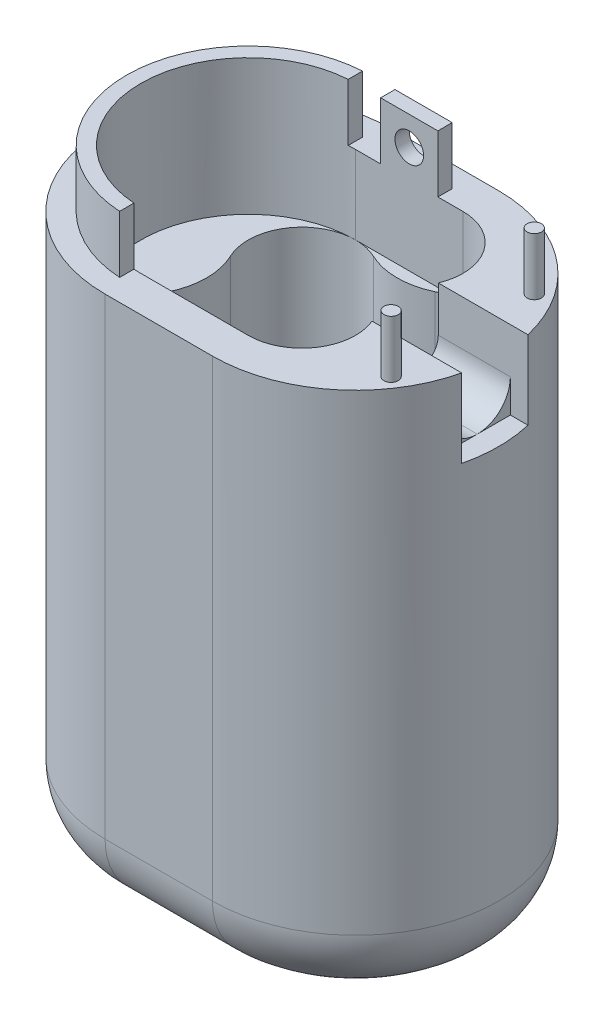
SolidWorks part; units mm, degrees
ref_plane "Front Plane" through (0, 0, 0) normal (0, 0, 1) x (1, 0, 0)
ref_plane "Top Plane" through (0, 0, 0) normal (0, 1, 0) x (1, 0, 0)
ref_plane "Right Plane" through (0, 0, 0) normal (1, 0, 0) x (0, 0, -1)
sketch "Sketch1" plane through (0, 0, 0) normal (0, 1, 0) x (1, 0, 0)
  line L0 (0, 0) -> (-23.105, 0) construction
  line L1 (-7.5, 0) -> (7.5, 0) construction
  line L2 (0, 13.7042) -> (0, -14.0987) construction
  line L3 (-7.5, 20) -> (7.5, 20)
  line L4 (-7.5, -20) -> (7.5, -20)
  arc A0 (-4.2857, 14.2763) -> (-14.2763, 4.2857) centre (-7.5, 7.5) ccw
  arc A1 (4.2857, 14.2763) -> (14.2763, 4.2857) centre (7.5, 7.5) cw
  arc A2 (4.2857, -14.2763) -> (14.2763, -4.2857) centre (7.5, -7.5) ccw
  arc A3 (-4.2857, -14.2763) -> (-14.2763, -4.2857) centre (-7.5, -7.5) cw
  arc A4 (14.2763, -4.2857) -> (14.2763, 4.2857) centre (23.3114, 0) cw
  arc A5 (-4.2857, -14.2763) -> (4.2857, -14.2763) centre (0, -23.3114) cw
  arc A6 (-14.2763, 4.2857) -> (-14.2763, -4.2857) centre (-23.3114, 0) cw
  arc A7 (-4.2857, 14.2763) -> (4.2857, 14.2763) centre (0, 23.3114) ccw
  arc A8 (-7.5, 20) -> (-7.5, -20) centre (-7.5, 0) ccw
  arc A9 (7.5, -20) -> (7.5, 20) centre (7.5, 0) ccw
  point P5 (0, 0)
  point P16 (7.5, 0)
  point P19 (0, -7.5)
  point P22 (-7.5, 0)
  point P25 (0, 7.5)
  dimension "D1" = 15
  dimension "D2" = 10
  dimension "D3" = 40
extrude "Boss-Extrude1" add sketch "Sketch1" along normal blind 55
sketch "Sketch2" plane through (0, 0, 0) normal (0, -1, 0) x (1, 0, 0)
  line L0 (-7.5, 0) -> (7.5, 0) construction
  line L1 (-7.5, 20) -> (7.5, 20)
  line L2 (-7.5, -20) -> (7.5, -20)
  line L3 (7.5, -20) -> (-7.5, -20) construction
  arc A0 (-7.5, 20) -> (-7.5, -20) centre (-7.5, 0) ccw
  arc A1 (7.5, -20) -> (7.5, 20) centre (7.5, 0) ccw
  arc A2 (-7.5, 20) -> (-7.5, -20) centre (-7.5, 0) ccw construction
  point P3 (0, 0)
extrude "Boss-Extrude2" add sketch "Sketch2" along normal blind 10
fillet "Fillet1" radius 10 4 edges at (27.5, -10, 0) (0, -10, -20) (-27.5, -10, 0) (0, -10, 20)
sketch "Sketch4" plane through (0, 55, 0) normal (0, 1, 0) x (1, 0, 0)
  line L0 (-7.5, -20) -> (7.5, -20) construction
  line L1 (-7.5, 20) -> (7.5, 20)
  line L2 (-7.5, -20) -> (7.5, -20)
  line L3 (27.5, 0) -> (27.5, 4.625) construction
  line L4 (14.4271, 4.625) -> (26.9579, 4.625)
  line L5 (7.5, 20) -> (-7.5, 20) construction
  line L6 (14.4271, -4.625) -> (26.9579, -4.625)
  line L7 (-7.5, 15) -> (7.5, 15)
  line L9 (27.5, 0) -> (27.5, -4.625) construction
  line L10 (7.5, -15) -> (-7.5, -15)
  arc A0 (-7.5, 20) -> (-7.5, -20) centre (-7.5, 0) ccw
  arc A1 (7.5, -20) -> (26.9579, -4.625) centre (7.5, 0) ccw
  arc A2 (-7.5, 20) -> (-7.5, -20) centre (-7.5, 0) ccw construction
  arc A3 (7.5, -15) -> (14.4271, -4.625) centre (7.5, -7.5) ccw
  arc A4 (-7.5, 15) -> (-7.5, -15) centre (-7.5, 0) ccw
  arc A5 (4.2857, -14.2763) -> (14.2763, -4.2857) centre (7.5, -7.5) ccw construction
  arc A6 (-14.2763, -4.2857) -> (-4.2857, -14.2763) centre (-7.5, -7.5) ccw construction
  arc A7 (14.4271, 4.625) -> (7.5, 15) centre (7.5, 7.5) ccw
  arc A12 (26.9579, 4.625) -> (7.5, 20) centre (7.5, 0) ccw
  arc A14 (7.5, -20) -> (7.5, 20) centre (7.5, 0) ccw construction
  point P3 (0, 0)
  dimension "D1" = 9.25
  dimension "D2" = 5
extrude "Boss-Extrude3" add sketch "Sketch4" along normal blind 10.95
fillet "Fillet3" radius 4.625 2 edges at (20.6925, 55, 4.625) (20.6925, 55, -4.625)
ref_plane "Plane1" through (27.5, 0, 0) normal (1, 0, 0) x (0, 0, -1)
sketch "Sketch5" plane through (27.5, 0, 0) normal (1, 0, 0) x (0, 0, -1)
  line L0 (4.625, 65.95) -> (4.625, 59.625) construction
  line L1 (-4.625, 65.95) -> (4.625, 65.95)
  line L2 (-4.625, 65.95) -> (-4.625, 55)
  line L3 (-4.625, 55) -> (4.625, 55)
  line L4 (4.625, 65.95) -> (4.625, 55)
extrude "Cut-Extrude1" cut sketch "Sketch5" against normal blind 3
sketch "Sketch6" plane through (0, 65.95, 0) normal (0, 1, 0) x (1, 0, 0)
  line L0 (-7.5, 15) -> (7.5, 15) construction
  line L1 (-4, 17) -> (4, 17)
  line L2 (-4, 17) -> (-4, 15)
  line L3 (-4, 15) -> (4, 15)
  line L4 (4, 17) -> (4, 15)
  line L5 (0, 15) -> (0, 0) construction
  line L8 (22.4666, 10) -> (22.4666, -10) construction
  line L9 (0, 0) -> (22.4666, 0) construction
  line L10 (22.4666, 10) -> (24.1296, 11.1111) construction
  line L11 (23.574, 11.9426) -> (24.6851, 10.2796) construction
  line L12 (22.4666, -10) -> (24.1296, -11.1111) construction
  line L13 (24.5, 0) -> (13.3114, 0) construction
  line L14 (23.574, -11.9426) -> (24.6851, -10.2796) construction
  line L15 (-8.5, 16.9706) -> (-8.5, 14.9666)
  line L16 (-8.5, -14.9666) -> (-8.5, -16.9706)
  circle A0 centre (22.4666, -10) radius 1
  circle A1 centre (22.4666, 10) radius 1
  arc A2 (-8.5, 14.9666) -> (-8.5, -14.9666) centre (-7.5, 0) ccw
  arc A3 (-8.5, 16.9706) -> (-8.5, -16.9706) centre (-7.5, 0) ccw
  arc A4 (-7.5, 15) -> (-7.5, -15) centre (-7.5, 0) ccw construction
  arc A5 (26.9579, 4.625) -> (7.5, 20) centre (7.5, 0) ccw construction
  arc A6 (7.5, -20) -> (26.9579, -4.625) centre (7.5, 0) ccw construction
  point P34 (24.1296, 11.1111)
  point P36 (24.1296, -11.1111)
  dimension "D4" = 15
  dimension "D5" = 1
  dimension "D6" = 2
  dimension "D3" = 17
  dimension "D1" = 2
  dimension "D2" = 8
  dimension "D7" = 20
  dimension "D8" = 2
extrude "Boss-Extrude4" add sketch "Sketch6" along normal blind 8
sketch "Sketch7" plane through (0, 0, -17) normal (0, 0, -1) x (-1, 0, 0)
  line L0 (-4, 73.95) -> (0, 69.95) construction
  line L1 (0, 69.95) -> (4, 73.95) construction
  line L2 (0, 69.95) -> (4, 65.95) construction
  circle A0 centre (0, 69.95) radius 2
  dimension "D1" = 4
extrude "Cut-Extrude2" cut sketch "Sketch7" against normal blind 8.2
